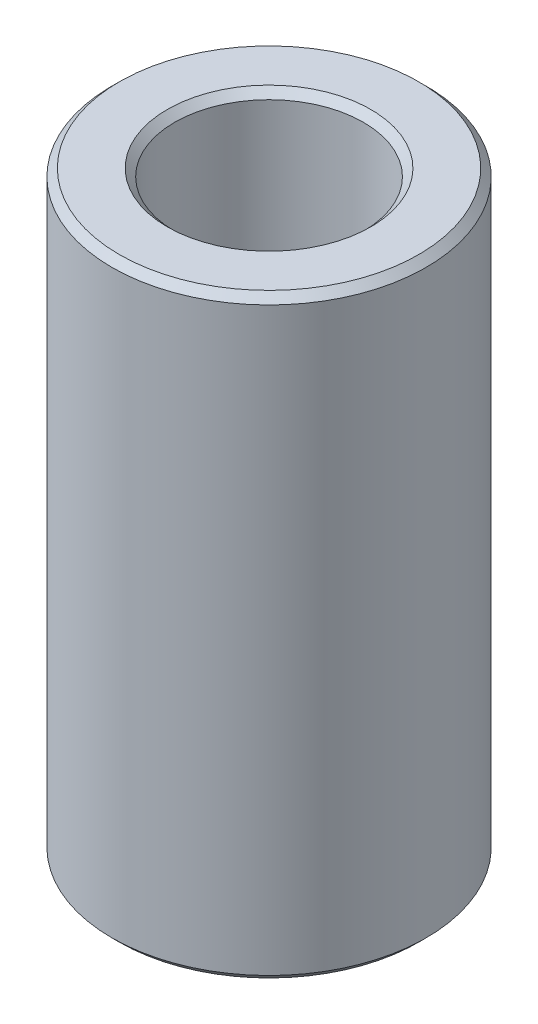
SolidWorks part; units mm, degrees
ref_plane "Front Plane" through (0, 0, 0) normal (0, 0, 1) x (1, 0, 0)
ref_plane "Top Plane" through (0, 0, 0) normal (0, 1, 0) x (1, 0, 0)
ref_plane "Right Plane" through (0, 0, 0) normal (1, 0, 0) x (0, 0, -1)
sketch "Sketch1" plane through (0, 0, 0) normal (0, 1, 0) x (1, 0, 0)
  circle A0 centre (0, 0) radius 37.5
  dimension "SLEEVE_OD" = 75
extrude "Boss-Extrude1" add sketch "Sketch1" along normal blind 142.1396
sketch "Sketch2" plane through (0, 0, 0) normal (0, 1, 0) x (1, 0, 0)
  circle A0 centre (0, 0) radius 22.5215
  dimension "BORE_D" = 45.0431
extrude "Cut-Extrude1" cut sketch "Sketch2" along normal through all
chamfer "Chamfer1" distance 1.7669 angle 45 4 edges at (0, 142.1396, 22.5215) (0, 0, 22.5215) (0, 0, 37.5) (0, 142.1396, 37.5)
